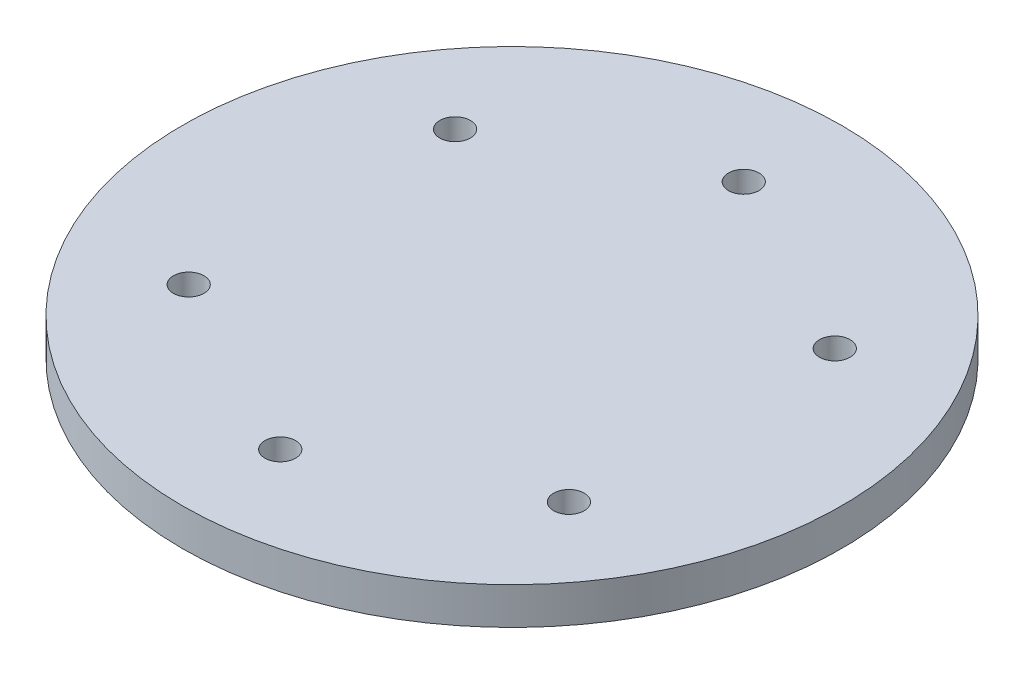
SolidWorks part; units mm, degrees
ref_plane "Front Plane" through (0, 0, 0) normal (0, 0, 1) x (1, 0, 0)
ref_plane "Top Plane" through (0, 0, 0) normal (0, 1, 0) x (1, 0, 0)
ref_plane "Right Plane" through (0, 0, 0) normal (1, 0, 0) x (0, 0, -1)
sketch "Sketch1" plane through (0, 0, 0) normal (0, 1, 0) x (1, 0, 0)
  circle A0 centre (0, 0) radius 35.55
  dimension "D1" = 71.1
extrude "Boss-Extrude1" add sketch "Sketch1" along normal blind 4
sketch "Sketch2" plane through (0, 4, 0) normal (0, 1, 0) x (1, 0, 0)
  line L0 (0, 0) -> (-35.55, 0) construction
  line L1 (0, 0) -> (-29.1209, 20.3906) construction
  line L2 (0, 0) -> (29.1209, 20.3906) construction
  line L3 (0, 35.55) -> (0, -35.55) construction
  line L4 (0, 0) -> (-29.1209, -20.3906) construction
  line L5 (0, 0) -> (29.1209, -20.3906) construction
  line L6 (0, 0) -> (35.55, 0) construction
  circle A0 centre (0, 0) radius 35.55 construction
  circle A2 centre (0, 25) radius 1.65
  circle A3 centre (-20.4788, 14.3394) radius 1.65
  circle A4 centre (20.4788, 14.3394) radius 1.65
  circle A5 centre (20.4788, -14.3394) radius 1.65
  circle A6 centre (0, -25) radius 1.65
  circle A7 centre (-20.3387, -14.5375) radius 1.65
  dimension "D2" = 25
  dimension "D3" = 3.3
  dimension "D1" = 35
  dimension "D4" = 35
  dimension "D5" = 35
  dimension "D6" = 35
  dimension "D7" = 55
extrude "Cut-Extrude1" cut sketch "Sketch2" against normal blind 10
